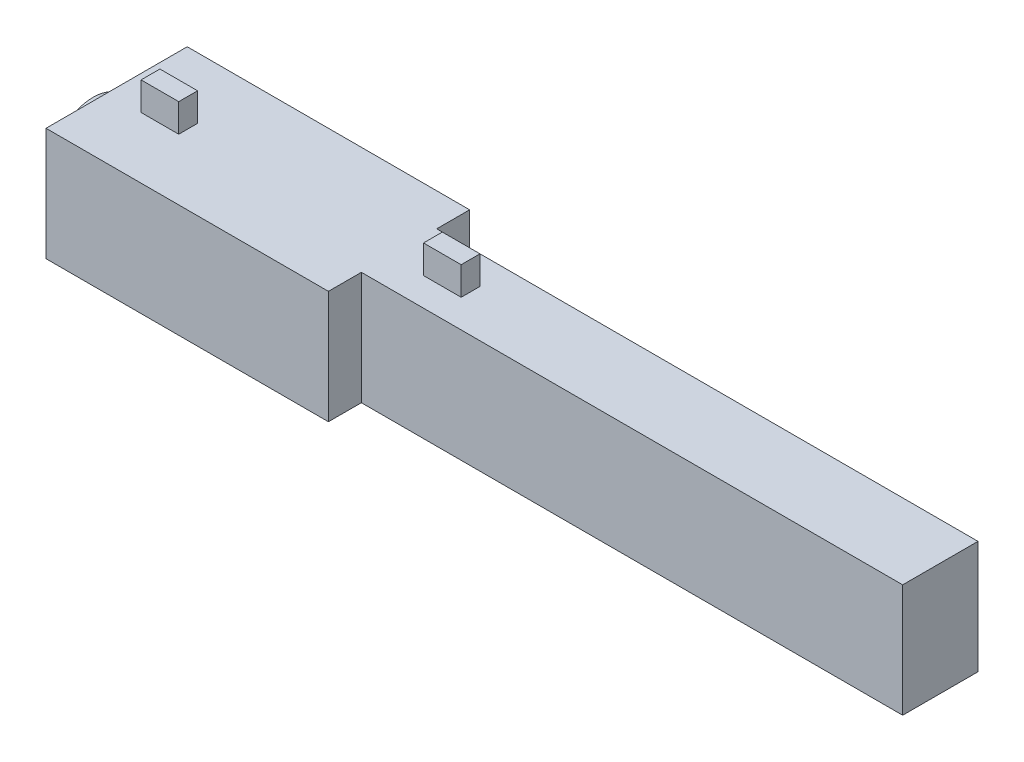
SolidWorks part; units mm, degrees
ref_plane "Plano frontal" through (0, 0, 0) normal (0, 0, 1) x (1, 0, 0)
ref_plane "Plano superior" through (0, 0, 0) normal (0, 1, 0) x (1, 0, 0)
ref_plane "Plano direito" through (0, 0, 0) normal (1, 0, 0) x (0, 0, -1)
sketch "Esboço1" plane through (0, 0, 0) normal (0, 0, 1) x (1, 0, 0)
  line L0 (-55.5, 5.35) -> (-55.5, -6.65)
  line L1 (-55.5, 5.35) -> (32, 5.35)
  line L2 (-55.5, -6.65) -> (32, -6.65)
  line L3 (32, -6.65) -> (32, 5.35)
  line L4 (-25.5, 5.35) -> (-25.5, -6.65)
  dimension "D1" = 30
  dimension "D2" = 12
extrude "Ressalto-extrusão1" add sketch "Esboço1" along normal blind 7.5 and the other way blind 7.5 contours L4 L1 L0 L2 region at (-40.5, -0.65, 0)
extrude "Ressalto-extrusão2" add sketch "Esboço1<3>" along normal blind 4 and the other way blind 4 contours L1 L4 L2 L3 region at (3.25, -0.65, 0)
sketch "Esboço1<3>" plane through (0, 0, 0) normal (0, 0, 1) x (1, 0, 0) same geometry as "Esboço1"
ref_plane "Plano1" through (-55.5, -6.65, -7.5) normal (0, -1, 0) x (-1, 0, 0)
sketch "Esboço2" plane through (-55.5, -6.65, -7.5) normal (0, -1, 0) x (-1, 0, 0)
  line L0 (-37.6, -6.5) -> (-37.6, -7.5)
  line L1 (-37.6, -7.5) -> (-37.6, -8.5)
  line L2 (-7.6, -7.5) -> (-7.6, -8.5)
  line L3 (-3.6, -7.5) -> (-3.6, -8.5)
  line L4 (-3.6, -8.5) -> (-7.6, -8.5)
  line L5 (-3.6, -7.5) -> (-3.6, -6.5)
  line L6 (-7.6, -7.5) -> (-7.6, -6.5)
  line L7 (-7.6, -6.5) -> (-3.6, -6.5)
  line L8 (-37.6, -8.5) -> (-33.6, -8.5)
  line L9 (-33.6, -8.5) -> (-33.6, -6.5)
  line L10 (-33.6, -6.5) -> (-37.6, -6.5)
  line L13 (-87.5, -7.5) -> (0, -7.5) construction
  line L14 (-87.5, -3.5) -> (-87.5, -11.5) construction
  line L15 (0, 0) -> (0, -15) construction
  point P3 (0, 0)
  point P12 (0, 0)
  point P13 (0, 0)
  point P21 (0, 0)
  point P22 (-33.6, -7.5)
  dimension "D1" = 2
extrude "Ressalto-extrusão3" add sketch "Esboço2" along normal blind 3
ref_plane "Plano2" through (-55.5, 5.35, -7.5) normal (0, -1, 0) x (-1, 0, 0)
sketch "Esboço3" plane through (-55.5, 5.35, -7.5) normal (0, -1, 0) x (-1, 0, 0)
  line L0 (-37.6, -6.5) -> (-37.6, -7.5)
  line L1 (-37.6, -7.5) -> (-37.6, -8.5)
  line L2 (-7.6, -7.5) -> (-7.6, -8.5)
  line L3 (-3.6, -7.5) -> (-3.6, -8.5)
  line L4 (-7.6, -8.5) -> (-3.6, -8.5)
  line L5 (-7.6, -7.5) -> (-7.6, -6.5)
  line L6 (-3.6, -7.5) -> (-3.6, -6.5)
  line L7 (-3.6, -6.5) -> (-7.6, -6.5)
  line L8 (-37.6, -8.5) -> (-33.6, -8.5)
  line L9 (-33.6, -8.5) -> (-33.6, -6.5)
  line L10 (-33.6, -6.5) -> (-37.6, -6.5)
  line L11 (-87.5, -7.5) -> (0, -7.5) construction
  line L12 (-87.5, -3.5) -> (-87.5, -11.5) construction
  line L13 (0, 0) -> (0, -15) construction
  point P17 (0, 0)
  point P18 (0, 0)
  point P19 (0, 0)
  point P20 (0, 0)
  point P21 (0, 0)
  point P22 (0, 0)
  dimension "D1" = 2
extrude "Ressalto-extrusão4" add sketch "Esboço3" against normal blind 3
ref_plane "Plano4" through (-55.5, 5.35, -7.5) normal (-1, 0, 0) x (0, 0, 1)
sketch "Esboço5" plane through (-55.5, 5.35, -7.5) normal (-1, 0, 0) x (0, 0, 1)
  circle A0 centre (7.5, -6.65) radius 4.5
  circle A2 centre (7.5, -6.65) radius 2.75
  dimension "D1" = 5.5
extrude "Ressalto-extrusão6" add sketch "Esboço1<9>" along normal blind 7.5 and the other way blind 7.5 contours L4 L1 L0 L2 region at (-40.5, -0.65, 0)
sketch "Esboço1<9>" plane through (0, 0, 0) normal (0, 0, 1) x (1, 0, 0) same geometry as "Esboço1"
sketch "Esboço6" plane through (-55.5, 0, 0) normal (-1, 0, 0) x (0, 0, 1)
extrude "Corte-extrusão1" cut sketch "Esboço5" against normal blind 72 contours A2 region at (-55.5, -1.3, 0)
extrude "Ressalto-extrusão7" add sketch "Esboço5<8>" along normal blind 2.5
sketch "Esboço5<8>" plane through (-55.5, 5.35, -7.5) normal (-1, 0, 0) x (0, 0, 1) same geometry as "Esboço5"
